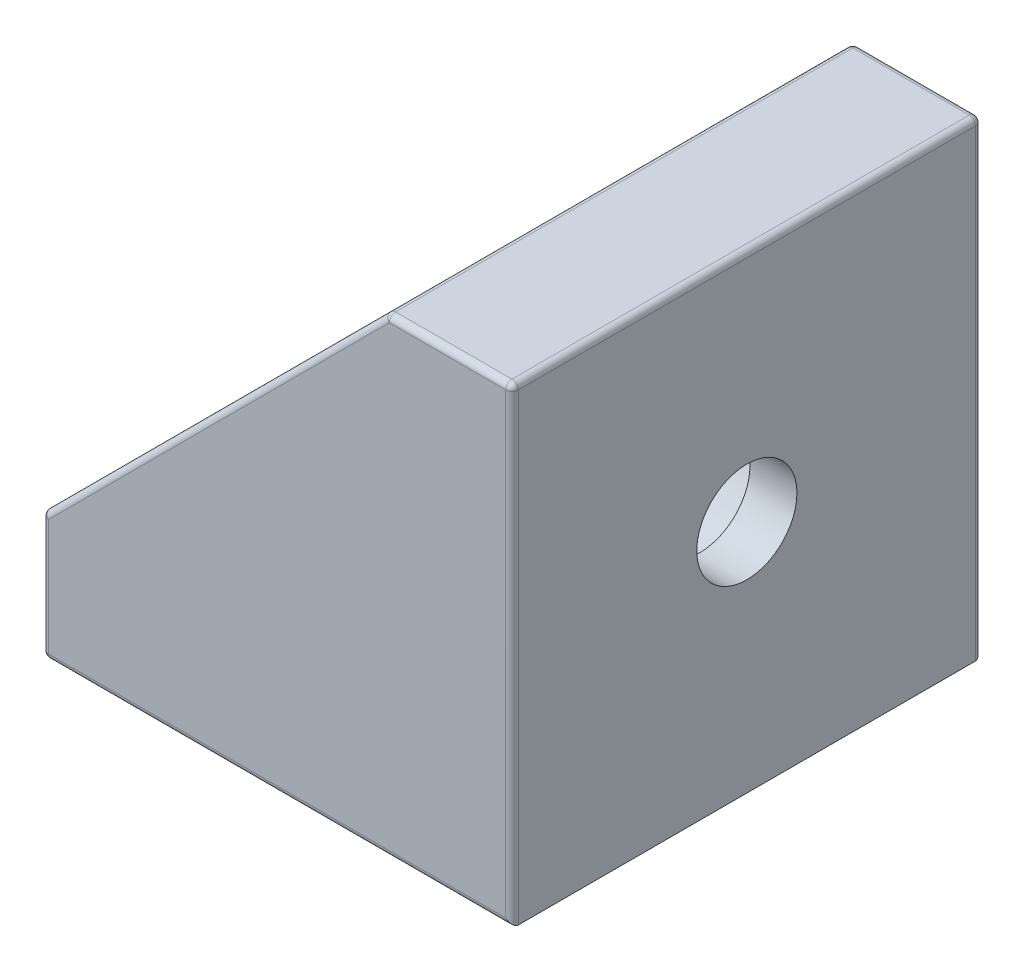
SolidWorks part; units mm, degrees
ref_plane "Front Plane" through (0, 0, 0) normal (0, 0, 1) x (1, 0, 0)
ref_plane "Top Plane" through (0, 0, 0) normal (0, 1, 0) x (1, 0, 0)
ref_plane "Right Plane" through (0, 0, 0) normal (1, 0, 0) x (0, 0, -1)
sketch "Sketch2" plane through (0, 0, 0) normal (0, 0, 1) x (1, 0, 0)
  line L0 (0, 0) -> (30, 0)
  line L1 (30, 0) -> (30, 30)
  line L2 (30, 30) -> (22, 30)
  line L3 (22, 30) -> (0, 8)
  line L4 (0, 8) -> (0, 0)
  dimension "D1" = 30
  dimension "D2" = 30
  dimension "D3" = 8
  dimension "D4" = 8
extrude "Boss-Extrude1" add sketch "Sketch2" along normal blind 30
sketch "Sketch3" plane through (30, 0, 0) normal (1, 0, 0) x (0, 0, -1)
  line L0 (-15, 30) -> (-15, 15) construction
  line L1 (-30, 30) -> (0, 30) construction
  circle A1 centre (-15, 15) radius 3.2
  dimension "D1" = 15
  dimension "D2" = 6.4
extrude "Cut-Extrude8" cut sketch "Sketch3" against normal blind 33
sketch "Sketch5" plane through (0, 0, 0) normal (0, -1, 0) x (1, 0, 0)
  line L0 (0, 15) -> (15, 15) construction
  line L1 (0, 30) -> (0, 0) construction
  circle A0 centre (15, 15) radius 3.2
  dimension "D2" = 6.4
  dimension "D1" = 15
extrude "Cut-Extrude5" cut sketch "Sketch5" against normal blind 32
sketch "Sketch7" plane through (0, 30, 0) normal (0, 1, 0) x (1, 0, 0)
  circle A0 centre (15, -15) radius 6
  circle A1 centre (15, -15) radius 3.2 construction
  circle A2 centre (15, -15) radius 3.2
  dimension "D1" = 12
sketch "Sketch8" plane through (0, 0, 0) normal (-1, 0, 0) x (0, 0, 1)
  circle A0 centre (15, 15) radius 6
  circle A1 centre (15, 15) radius 3.2 construction
  circle A2 centre (15, 15) radius 3.2
  dimension "D1" = 12
extrude "Cut-Extrude9" cut sketch "Sketch8" against normal blind 27
extrude "Cut-Extrude10" cut sketch "Sketch7" against normal blind 27
fillet "Fillet6" radius 0.4 16 edges at (30, 30, 15) (26, 30, 30) (30, 15, 30) (15, 0, 30) (0, 4, 30) (0, 0, 15) (15, 0, 0) (30, 15, 0) (26, 30, 0) (0, 4, 0) (22, 30, 15) (11, 19, 30) (0, 8, 15) (11, 19, 0) (1, 9, 15) (21, 29, 15)
